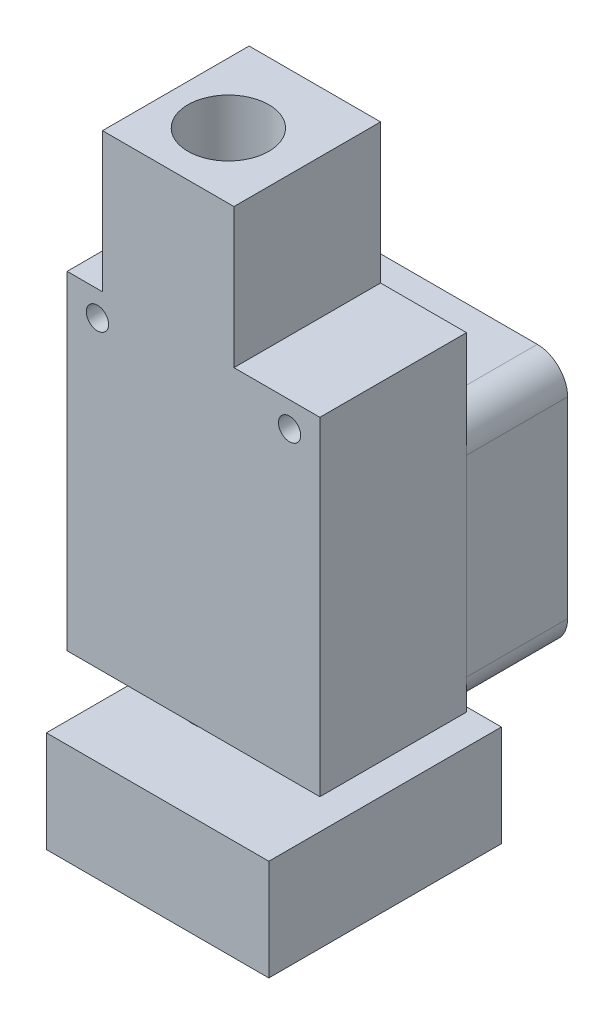
SolidWorks part; units mm, degrees
material "6061 Alloy"
ref_plane "Front Plane" through (0, 0, 0) normal (0, 0, 1) x (1, 0, 0)
ref_plane "Top Plane" through (0, 0, 0) normal (0, 1, 0) x (1, 0, 0)
ref_plane "Right Plane" through (0, 0, 0) normal (1, 0, 0) x (0, 0, -1)
sketch "Sketch1" plane through (0, 0, 0) normal (0, 0, 1) x (1, 0, 0)
  line L0 (0, -281.9642) -> (0, 13816.245) construction
  line L1 (7, 0) -> (-6, 0)
  line L2 (-6, 0) -> (-6, -13.8)
  line L3 (-6, -13.8) -> (-9.5, -13.8)
  line L4 (-9.5, -13.8) -> (-9.5, -46.3)
  line L5 (-9.5, -46.3) -> (15.5, -46.3)
  line L6 (15.5, -46.3) -> (15.5, -13.8)
  line L7 (15.5, -13.8) -> (7, -13.8)
  line L8 (7, -13.8) -> (7, 0)
  line L9 (-6.5, -16.3) -> (12.5, -16.3) construction
  line L10 (-6.5, -49.3) -> (15.5, -49.3)
  line L11 (15.5, -49.3) -> (15.5, -59.3)
  line L12 (15.5, -59.3) -> (-6.5, -59.3)
  line L13 (-6.5, -59.3) -> (-6.5, -49.3)
  line L14 (0, -46.3) -> (0, -68)
  line L15 (0.4, -68) -> (3.5, -63.96)
  line L16 (3.5, -63.96) -> (3.5, -46.3)
  line L17 (0.875, -46.3) -> (0.875, -6)
  line L18 (0, 0) -> (0, -46.3)
  line L19 (0.875, -6) -> (4, -6)
  line L20 (4, -6) -> (4, 0)
  line L21 (0.4, -68) -> (0.2, -68)
  line L22 (0.2, -68) -> (0.2, -66)
  line L23 (0.2, -66) -> (0.875, -46.3)
  line L24 (0.2, -68) -> (0, -68)
  circle A0 centre (-6.5, -16.3) radius 1.1
  circle A1 centre (12.5, -16.3) radius 1.1
  dimension "D8" = 3
  dimension "D9" = 3
  dimension "D10" = 2.2
  dimension "D20" = 6.5
  dimension "D21" = 12.5
  dimension "D1" = 13
  dimension "D2" = 7
  dimension "D3" = 13.8
  dimension "D4" = 32.5
  dimension "D5" = 3.5
  dimension "D6" = 8.5
  dimension "D7" = 2.5
  dimension "D11" = 3
  dimension "D12" = 10
  dimension "D13" = 3
  dimension "D14" = 68
  dimension "D15" = 37.5
  dimension "D16" = 7
  dimension "D17" = 0.875
  dimension "D18" = 4
  dimension "D19" = 6
  dimension "D22" = 0.4
  dimension "D23" = 0.2
  dimension "D24" = 2
extrude "Boss-Extrude1" add sketch "Sketch1" along normal blind 6.45 and the other way blind 8.05 contours L7 L8 L1 L2 L3 L4 L5 L6 A1 A0 | L16 L12 L11 L10 | L14 L10 L13 L12 | L12 L16 L10 L14 | L18 L1 L2 L3 L4 L5 A0 | L1 L18 L5 L17 | L12 L23 L10 L14 region at (7.689, -27.4493, 0) region at (3.5353, -3, 0) region at (-4.3591, -25.2413, 0) region at (-3.25, -54.3, 0) region at (0.3086, -53.8248, 0) region at (2.0488, -54.3985, 0) region at (9.5, -54.3, 0)
extrude "Boss-Extrude2" add sketch "Sketch1<7>" along normal mid plane 23 contours L14 L10 L13 L12 | L12 L23 L10 L14 | L23 L12 L16 L10 | L16 L12 L11 L10 region at (-3.25, -54.3, 0) region at (0.3086, -53.8248, 0) region at (2.0488, -54.3985, 0) region at (9.5, -54.3, 0)
sketch "Sketch1<7>" plane through (0, 0, 0) normal (0, 0, 1) x (1, 0, 0) same geometry as "Sketch1"
revolve "Revolve1" add sketch "Sketch1<3>" angle 360 about L0 region at (2.1616, -47.8096, 0) region at (2.0488, -54.3985, 0) region at (1.7277, -62.8576, 0)
sketch "Sketch1<3>" plane through (0, 0, 0) normal (0, 0, 1) x (1, 0, 0) same geometry as "Sketch1"
revolve "Cut-Revolve1" cut sketch "Sketch1<6>" angle 360 about L0 region at (3.5353, -3, 0)
sketch "Sketch1<6>" plane through (0, 0, 0) normal (0, 0, 1) x (1, 0, 0) same geometry as "Sketch1"
sketch "Sketch2" plane through (0, 0, -8.05) normal (0, 0, -1) x (-1, 0, 0)
  line L1 (-15.8, -46.9) -> (9.8, -46.9)
  line L2 (-15.8, -46.9) -> (-15.8, -21.3)
  line L3 (-15.8, -21.3) -> (9.8, -21.3)
  line L4 (9.8, -46.9) -> (9.8, -21.3)
  line L5 (-3, -21.3) -> (-3, -46.9) construction
  line L6 (-15.8, -34.1) -> (9.8, -34.1) construction
  circle A0 centre (6.5, -16.3) radius 1.1 construction
  circle A1 centre (-3, -34.1) radius 11
  circle A2 centre (-3, -34.1) radius 5
  point P0 (-3, -34.1)
  line M10 (-15.5, -13.8) -> (-15.5, -46.3)
  line M11 (-15.5, -46.3) -> (9.5, -46.3)
  line M12 (9.5, -46.3) -> (9.5, -13.8)
  dimension "D4" = 5
  dimension "D5" = 22
  dimension "D6" = 10
  dimension "D1" = 3
  dimension "D2" = 25.6
  dimension "D3" = 25.6
extrude "Boss-Extrude3" add sketch "Sketch2" along normal blind 10 separate body contours L3 A1 M10 M11 M12 | A2 | A1 A2 region at (3, -21.6536, -8.05) region at (13.6889, -34.1, -8.05) region at (3, -34.1, -8.05)
extrude "Cut-Extrude1" cut sketch "Sketch2<3>" against normal blind 3 from surface contours A1 A2 region at (13.6889, -34.1, -8.05) starting at face at (3, -33.8, -18.05)
sketch "Sketch2<3>" plane through (0, 0, -8.05) normal (0, 0, -1) x (-1, 0, 0) same geometry as "Sketch2"
fillet "Fillet1" radius 3 4 edges at (-9.5, -46.3, -13.05) (15.5, -46.3, -13.05) (-9.5, -21.3, -13.05) (15.5, -21.3, -13.05)
